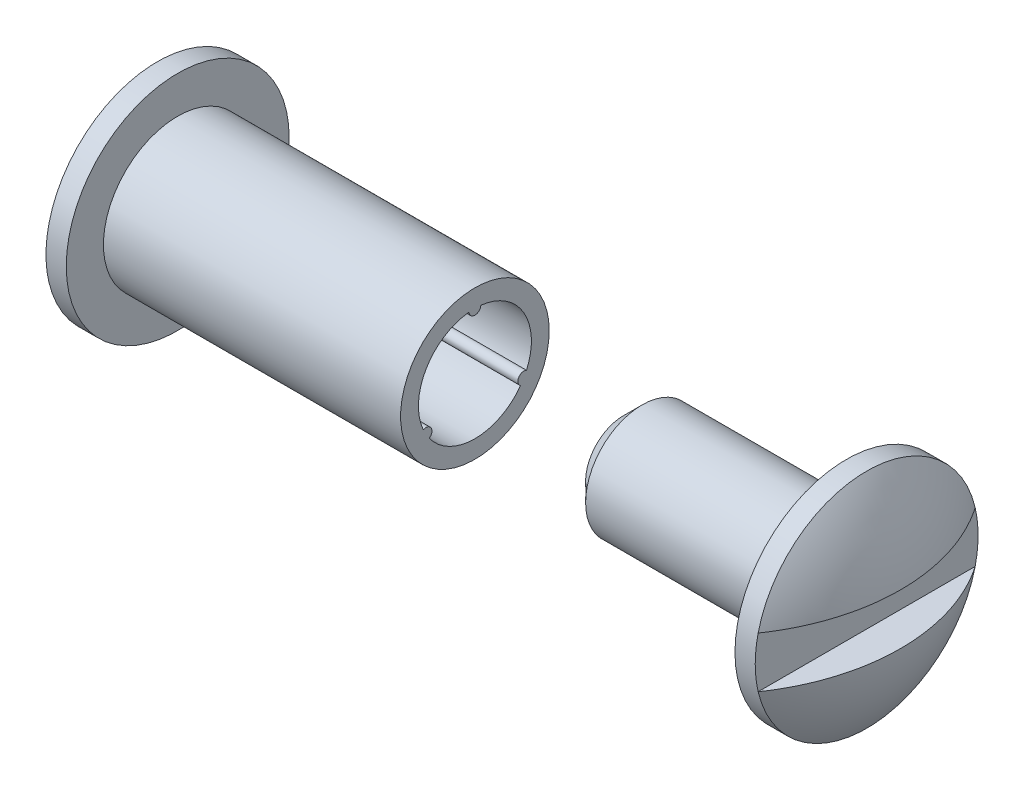
SolidWorks part; units mm, degrees
ref_plane "Front Plane" through (0, 0, 0) normal (0, 0, 1) x (1, 0, 0)
ref_plane "Top Plane" through (0, 0, 0) normal (0, 1, 0) x (1, 0, 0)
ref_plane "Right Plane" through (0, 0, 0) normal (1, 0, 0) x (0, 0, -1)
sketch "Sketch1" plane through (0, 0, 0) normal (0, 0, 1) x (1, 0, 0)
  line L0 (0, 0) -> (9.525, 0) construction
  line L1 (0, 2.413) -> (0, -2.413) construction
  line L2 (9.525, 4.7625) -> (9.525, -4.7625) construction
  line L3 (9.525, 0) -> (11.905, 0) construction
  line L4 (-6.35, 3.175) -> (-6.35, -3.175) construction
  line L5 (-6.35, 0) -> (-19.05, 0) construction
  line L6 (-19.05, 4.7625) -> (-19.05, -4.7625) construction
  line L7 (-6.35, 2.413) -> (-12.7, 2.413) construction
  line L8 (-12.7, 2.413) -> (-12.7, -2.413) construction
  line L9 (-12.7, -2.413) -> (-6.35, -2.413) construction
  line L10 (-19.05, 0) -> (-21.43, 0) construction
  line L11 (9.525, -4.7625) -> (-19.05, -4.7625) construction
  point P18 (-12.7, 0)
  point P19 (-4.7625, -4.7625)
  point P21 (2.6458, -2.413)
  dimension "D1" = 6.35
  dimension "D2" = 2.6458
ref_plane "Plane1" through (11.905, 0, 0) normal (1, 0, 0) x (0, 0, -1)
sketch "Sketch2" plane through (0, 0, 0) normal (1, 0, 0) x (0, 0, -1)
  circle A0 centre (0, 0) radius 2.413
extrude "Boss-Extrude1" add sketch "Sketch2" along normal up to vertex (9.525 mm away) up to point (9.525, 0, 0)
sketch "Sketch4" plane through (0, 0, 0) normal (-1, 0, 0) x (0, 0, 1)
  circle A1 centre (0, 0) radius 2.413
  circle A2 centre (0, 0) radius 2.413
  dimension "D1" = 0
chamfer "Chamfer1" distance 0.7937 angle 45 1 edges at (0, 0, -2.413)
curve "Helix/Spiral1" [suppressed] pitch 1.0583 height 10.5833 turns 10 parameters "Pitch"=1.0583
sketch "Sketch5" plane through (0, 0, 0) normal (0, 0, 1) x (1, 0, 0)
  line L0 (0, 2.413) -> (-0.926, 2.413)
  line L1 (0, 2.413) -> (-0.3969, 1.7256)
  line L2 (-0.3969, 1.7256) -> (-0.5292, 1.7256)
  line L3 (-0.5292, 1.7256) -> (-0.926, 2.413)
  line L4 (-0.463, 1.7256) -> (-0.463, 2.413) construction
  line L5 (-0.1984, 2.0693) -> (-0.7276, 2.0693) construction
  dimension "D1" = 0.1323
  dimension "D2" = 0.5292
  dimension "D3" = 60
sweep "Cut-Sweep1" [suppressed] cut profiles "Sketch5" path "Helix/Spiral1"
sketch "Sketch6" plane through (0, 0, 0) normal (0, 0, 1) x (1, 0, 0)
  line L0 (9.525, 0) -> (9.525, 4.7625)
  line L1 (9.525, 4.7625) -> (10.3904, 4.7625)
  line L2 (11.905, 0) -> (11.905, 4.7625) construction
  line L3 (11.905, 0) -> (9.525, 0) construction
  line L5 (9.525, 0) -> (11.905, 0)
  line L6 (11.905, 0) -> (11.905, -1.9812) construction
  arc A0 (11.905, 0) -> (10.3904, 4.7625) centre (3.6598, 0) ccw
  point P10 (11.905, -1.9812)
  dimension "D1" = 0.8654
revolve "Revolve1" add sketch "Sketch6" angle 360 about L3
ref_plane "Plane2" through (-4.7625, 0, 0) normal (1, 0, 0) x (0, 0, -1)
sketch "Sketch17" plane through (11.905, 0, 0) normal (1, 0, 0) x (0, 0, -1)
  line L0 (-4.7625, 0) -> (4.7625, 0) construction
  line L1 (-4.7625, 1.0858) -> (4.7625, 1.0858)
  line L2 (-4.7625, 1.0858) -> (-4.7625, -1.0858)
  line L3 (-4.7625, -1.0858) -> (4.7625, -1.0858)
  line L4 (4.7625, 1.0858) -> (4.7625, -1.0858)
  circle A0 centre (0, 0) radius 4.7625 construction
  dimension "D1" = 2.1717
extrude "Cut-Extrude5" cut sketch "Sketch17" against normal up to vertex (1.5145 mm away) up to point (10.3904, 4.7625, 0)
mirror "Mirror1" about plane through (-4.7625, 0, 0) normal (1, 0, 0) of bodies 118 107 106
ref_plane "Plane3" through (-6.35, 0, 0) normal (1, 0, 0) x (0, 0, -1)
sketch "Sketch11" plane through (-6.35, 0, 0) normal (1, 0, 0) x (0, 0, -1)
  line L0 (0, 2.413) -> (0, 0) construction
  line L1 (0, 0) -> (-2.0897, -1.2065) construction
  line L2 (0, 0) -> (2.0897, -1.2065) construction
  circle A0 centre (0, 0) radius 3.175
  arc A1 (-0.2536, 2.3996) -> (-2.205, -0.9802) centre (0, 0) ccw
  arc A2 (-1.9513, -1.4195) -> (-2.205, -0.9802) centre (-2.0897, -1.2065) ccw
  arc A3 (-0.2536, 2.3996) -> (0.2536, 2.3996) centre (0, 2.413) ccw
  arc A4 (2.205, -0.9802) -> (1.9513, -1.4195) centre (2.0897, -1.2065) ccw
  arc A5 (2.205, -0.9802) -> (0.2536, 2.3996) centre (0, 0) ccw
  arc A6 (-1.9513, -1.4195) -> (1.9513, -1.4195) centre (0, 0) ccw
  dimension "D3" = 0.508
  dimension "D1" = 120
  dimension "D2" = 120
extrude "Boss-Extrude3" add sketch "Sketch11" against normal up to surface (12.7 mm away) separate body
combine bodies "Combine1" operation type add bodies to combine 111 110
combine bodies "Combine2" operation type add bodies to combine 118 101
equation "\"D1@Sketch5\" = \"Pitch@Helix/Spiral1\"*.125"
equation "\"D2@Sketch5\" = \"Pitch@Helix/Spiral1\"*.50"
equation "\"D3@Helix/Spiral1\" = \"Screw Length@Sketch1\"+\"Pitch@Helix/Spiral1\""
equation "\"D1@Chamfer1\" = \"Pitch@Helix/Spiral1\"*.750"
equation "\"D1@Sketch6\" = \"Head Height@Sketch1\"/2.75"
equation "\"D2@Sketch1\" = \"Pitch@Helix/Spiral1\"*2.50"
equation "\"D1@Sketch17\" = \"Screw Dia@Sketch1\"*.45"
